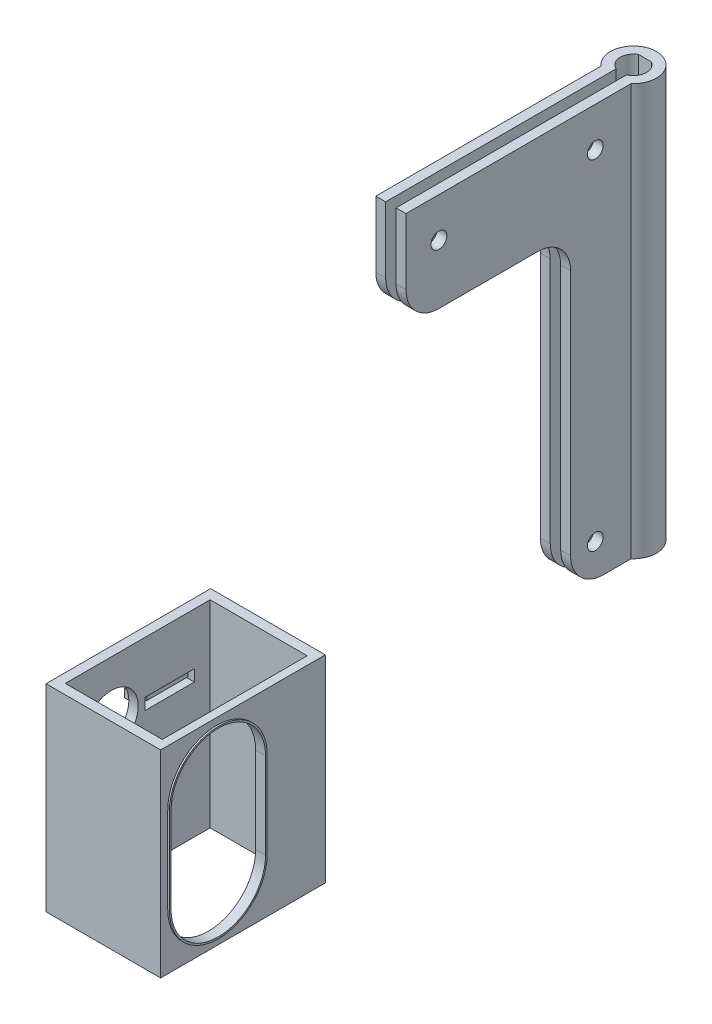
SolidWorks part; units mm, degrees
ref_plane "Front Plane" through (0, 0, 0) normal (0, 0, 1) x (1, 0, 0)
ref_plane "Top Plane" through (0, 0, 0) normal (0, 1, 0) x (1, 0, 0)
ref_plane "Right Plane" through (0, 0, 0) normal (1, 0, 0) x (0, 0, -1)
ref_plane "ULTRASONIC CENTER" through (0, 0, 125) normal (0, 0, 1) x (1, 0, 0)
sketch "Sketch1" plane through (0, 0, 0) normal (0, 1, 0) x (1, 0, 0)
  line L0 (-1.5875, -3.6715) -> (-1.5875, -23.6715)
  line L1 (1.5875, -3.6715) -> (1.5875, -23.6715)
  line L2 (1.9365, 3.5) -> (-1.9365, 3.5)
  line L3 (4.5875, -5.2872) -> (4.5875, -23.6715)
  line L4 (-4.5875, -5.2872) -> (-4.5875, -23.6715)
  line L5 (-4.5875, -23.6715) -> (-1.5875, -23.6715)
  line L6 (1.5875, -23.6715) -> (4.5875, -23.6715)
  arc A0 (1.5875, -3.6715) -> (1.9365, 3.5) centre (0, 0) ccw
  arc A1 (4.5875, -5.2872) -> (-4.5875, -5.2872) centre (0, 0) ccw
  arc A2 (-1.9365, 3.5) -> (-1.5875, -3.6715) centre (0, 0) ccw
  arc A4 (1.5875, -3.6715) -> (-1.5875, -3.6715) centre (0, 0) ccw construction
  dimension "D1" = 4
  dimension "D2" = 20
  dimension "D3" = 3.5
  dimension "D5" = 3.175
  dimension "D4" = 3
extrude "Boss-Extrude1" add sketch "Sketch1" along normal blind 125
ref_plane "PADDLE CENTER" through (0, 0, 0) normal (-1, 0, 0) x (0, 0, 1)
ref_plane "DISC CENTER" through (0, -15, 0) normal (0, 1, 0) x (1, 0, 0)
ref_axis "Axis1" through (0, -15, 24.6715) along (0, 0, -1)
ref_plane "OFFSET" through (-36.4125, 0, 0) normal (-1, 0, 0) x (0, 0, 1)
ref_plane "PADDLE SURFACE" through (-1.5875, 0, 0) normal (1, 0, 0) x (0, 0, -1)
ref_axis "Axis2" through (-36.4125, -15, -8.5336) along (0, 0, 1)
ref_point "ULTRASONIC"
sketch "Sketch5" plane through (0, 125, 0) normal (0, 1, 0) x (1, 0, 0)
  line L1 (-1.5875, -111.5) -> (-1.5875, -106.5)
  line L2 (-47.5875, -106.5) -> (-47.5875, -141.5)
  line L3 (-47.5875, -141.5) -> (-1.5875, -141.5)
  line L4 (-1.5875, -141.5) -> (-1.5875, -136.5)
  line L5 (-1.5875, -136.5) -> (-42.5875, -136.5)
  line L9 (-1.5875, -23.6715) -> (-1.5875, -3.6715) construction
  line L10 (-42.5875, -111.5) -> (-1.5875, -111.5)
  line L12 (-42.5875, -136.5) -> (-42.5875, -111.5)
  line L13 (-47.5875, -106.5) -> (-1.5875, -106.5)
  line L18 (-18.6703, -4) -> (17.7565, -4) construction
  circle A0 centre (0, 0) radius 4 construction
  arc A1 (-1.9365, 3.5) -> (-1.5875, -3.6715) centre (0, 0) ccw construction
  point P2 (-42.5875, -124)
  dimension "D2" = 120
  dimension "D1" = 41
  dimension "D3" = 25
  dimension "D4" = 5
  dimension "D5" = 5
  dimension "D7" = 5
extrude "Boss-Extrude2" [suppressed] add sketch "Sketch5" against normal mid plane 30 from offset 137.5 offset against normal yes
sketch "Sketch6" plane through (0, 125, 0) normal (0, 1, 0) x (1, 0, 0)
  line L0 (4.5875, -23.6715) -> (4.5875, -5.2872) construction
  line L1 (1.5875, -23.6715) -> (4.5875, -23.6715)
  line L2 (1.5875, -23.6715) -> (1.5875, -73.6715)
  line L3 (1.5875, -73.6715) -> (4.5875, -73.6715)
  line L4 (4.5875, -23.6715) -> (4.5875, -73.6715)
  line L6 (-1.5875, -23.6715) -> (-1.5875, -3.6715) construction
  line L7 (-4.5875, -23.6715) -> (-1.5875, -23.6715)
  line L8 (-4.5875, -23.6715) -> (-4.5875, -73.6715)
  line L9 (-4.5875, -73.6715) -> (-1.5875, -73.6715)
  line L10 (-1.5875, -23.6715) -> (-1.5875, -73.6715)
  dimension "D1" = 50
extrude "Boss-Extrude3" add sketch "Sketch6" against normal blind 30
fillet "Fillet6" radius 10 6 edges at (3.0875, 0, 23.6715) (-3.0875, 0, 23.6715) (3.0875, 95, 73.6715) (-3.0875, 95, 73.6715) (3.0875, 95, 23.6715) (-3.0875, 95, 23.6715)
hole_wizard "M4 Clearance Hole1" positions "Sketch2" profile "Sketch3" hole size "M4" standard "ANSI Metric" end condition through all
sketch "Sketch2" plane through (4.5875, 0, 0) normal (1, 0, 0) x (0, 0, -1)
  line L4 (-73.6715, 125) -> (-5.2872, 125) construction
  line L6 (-73.6715, 105) -> (-73.6715, 125) construction
  point P0 (-16.1715, 113)
  point P4 (-16.1715, 10)
  point P19 (-63.6715, 113)
  dimension "D1" = 103
  dimension "D2" = 12
  dimension "D3" = 47.5
  dimension "D4" = 10
sketch "Sketch3" plane through (4.5875, 113, 16.1715) normal (0, 1, 0) x (0, 0, -1)
  line L0 (0, 0) -> (0, 11.5875)
  line L1 (0, 11.5875) -> (2.4, 11.5875)
  line L2 (2.4, 11.5875) -> (2.4, 0)
  line L5 (2.4, 0) -> (0, 0)
  line L11 (0, -6.35) -> (0, 107.95) construction
  dimension "Thru Hole Dia." = 4.8
  dimension "Thru Hole Depth" = 11.5875
sketch "Sketch9" [suppressed] plane through (-1.5875, 0, 0) normal (1, 0, 0) x (0, 0, -1)
  line L0 (-105.675, 2.5) -> (-22.7496, 2.5)
  line L1 (-105.675, 2.5) -> (-105.675, -27.5)
  line L2 (-105.675, -27.5) -> (-22.7496, -27.5)
  line L3 (-22.7496, 95) -> (-22.7496, 0) construction
  line L5 (-4.1335, 0) -> (-4.1335, -27.5)
  line L6 (-4.1335, -27.5) -> (-22.7496, -27.5)
  line L7 (-22.7496, 2.5) -> (-22.7496, 0)
  line L8 (-22.7496, 95) -> (-22.7496, 0) construction
  line L9 (-22.7496, 0) -> (-4.1335, 0) construction
  line L10 (-22.7496, 0) -> (-4.1335, 0)
extrude "Boss-Extrude5" [suppressed] add sketch "Sketch9" against normal up to surface (3 mm away) up to face at (-4.5875, 113, 13.7715)
chamfer "Chamfer2" [suppressed] distance 42 distance2 35
fillet "Fillet1" [suppressed] radius 40
fillet "Fillet2" [suppressed] radius 10
sketch "Sketch11" plane through (0, 125, 0) normal (0, 1, 0) x (1, 0, 0)
  line L0 (-21.2191, -4) -> (29.064, -4) construction
  line L1 (4.5875, -66.5) -> (47.5875, -66.5)
  line L2 (4.5875, -73.6715) -> (4.5875, -5.2872) construction
  line L3 (47.5875, -66.5) -> (47.5875, -101.5)
  line L4 (47.5875, -101.5) -> (4.5875, -101.5)
  line L5 (4.5875, -101.5) -> (4.5875, -96.5)
  line L6 (4.5875, -96.5) -> (42.5875, -96.5)
  line L7 (42.5875, -96.5) -> (42.5875, -71.5)
  line L8 (42.5875, -71.5) -> (4.5875, -71.5)
  line L9 (4.5875, -71.5) -> (4.5875, -66.5)
  line L10 (1.5875, -3.6715) -> (1.5875, -73.6715) construction
  circle A0 centre (0, 0) radius 4 construction
  arc A1 (-1.9365, 3.5) -> (-1.5875, -3.6715) centre (0, 0) ccw construction
  point P17 (42.5875, -84)
  dimension "D1" = 5
  dimension "D2" = 5
  dimension "D3" = 5
  dimension "D4" = 41
  dimension "D5" = 80
  dimension "D6" = 25
extrude "Boss-Extrude6" [suppressed] add sketch "Sketch11" along normal mid plane 30 from offset 137.5 offset against normal yes
sketch "Sketch13" [suppressed] plane through (4.5875, 0, 0) normal (-1, 0, 0) x (0, 0, 1)
  line L0 (70.675, 2.5) -> (22.7496, 2.5)
  line L1 (22.7496, 55) -> (22.7496, 42.5) construction
  line L2 (22.7496, 2.5) -> (22.7496, 0)
  line L3 (22.7496, 0) -> (4.1335, 0)
  line L4 (70.675, 2.5) -> (70.675, -27.5)
  line L5 (70.675, -27.5) -> (4.1335, -27.5)
  line L6 (4.1335, -27.5) -> (4.1335, 0)
extrude "Boss-Extrude8" [suppressed] add sketch "Sketch13" along normal up to surface (3 mm away) up to face at (1.5875, 113, 13.7715)
chamfer "Chamfer3" [suppressed] distance 42 distance2 35
fillet "Fillet5" [suppressed] radius 40
fillet "Fillet4" [suppressed] radius 10
sketch "Sketch14" [suppressed] plane through (0, 0, 110.675) normal (0, 0, 1) x (1, 0, 0)
  line L5 (-47.5875, -27.5) -> (-47.5875, 2.5) construction
  line L6 (-40.0875, -7.5) -> (-40.0875, -17.5) construction
  line L7 (-37.5875, -7.5) -> (-37.5875, -17.5)
  line L8 (-42.5875, -7.5) -> (-42.5875, -17.5)
  line L9 (-42.5875, -27.5) -> (-42.5875, 2.5) construction
  arc A0 (-37.5875, -7.5) -> (-42.5875, -7.5) centre (-40.0875, -7.5) ccw
  arc A1 (-42.5875, -17.5) -> (-37.5875, -17.5) centre (-40.0875, -17.5) ccw
  point P2 (-40.0875, -12.5)
  point P9 (-47.5875, -12.5)
  dimension "D1" = 5
  dimension "D2" = 10
extrude "Cut-Extrude1" [suppressed] cut sketch "Sketch14" against normal up to next
sketch "Sketch15" [suppressed] plane through (0, 0, 70.675) normal (0, 0, 1) x (1, 0, 0)
  line L0 (40.0875, -7.5) -> (40.0875, -17.5) construction
  line L1 (42.5875, -7.5) -> (42.5875, -17.5)
  line L2 (37.5875, -7.5) -> (37.5875, -17.5)
  line L3 (42.5875, 2.5) -> (42.5875, -27.5) construction
  arc A0 (42.5875, -7.5) -> (37.5875, -7.5) centre (40.0875, -7.5) ccw
  arc A1 (37.5875, -17.5) -> (42.5875, -17.5) centre (40.0875, -17.5) ccw
  point P2 (40.0875, -12.5)
  point P9 (42.5875, -12.5)
  dimension "D1" = 5
  dimension "D2" = 10
extrude "Cut-Extrude2" [suppressed] cut sketch "Sketch15" against normal up to next
sketch "Sketch16" plane through (-36.4125, 0, 0) normal (-1, 0, 0) x (0, 0, 1)
  line L0 (125, 15) -> (125, -45) construction
  line L1 (92, 15) -> (142, 15)
  line L3 (92, -45) -> (142, -45)
  line L4 (142, 15) -> (142, -45)
  line L5 (92, 15) -> (142, -45) construction
  line L6 (92, -45) -> (142, 15) construction
  line L7 (132.5, -11) -> (132.5, -19) construction
  line L12 (92, 15) -> (92, -45)
  line L13 (134.75, -11) -> (134.75, -19)
  line L14 (130.25, -11) -> (130.25, -19)
  line L15 (116.35, -10) -> (116.35, -20) construction
  line L16 (117.35, -10) -> (117.35, -20)
  line L17 (115.35, -10) -> (115.35, -20)
  circle A0 centre (125, -2) radius 8.15
  circle A1 centre (125, -28) radius 8.15
  arc A4 (134.75, -11) -> (130.25, -11) centre (132.5, -11) ccw
  arc A5 (130.25, -19) -> (134.75, -19) centre (132.5, -19) ccw
  arc A6 (117.35, -10) -> (115.35, -10) centre (116.35, -10) ccw
  arc A7 (115.35, -20) -> (117.35, -20) centre (116.35, -20) ccw
  point P1 (117, -15)
  point P14 (125, -15)
  point P15 (132.5, -15)
  point P26 (116.35, -15)
  dimension "D4" = 16.3
  dimension "D5" = 16.3
  dimension "D1" = 60
  dimension "D3" = 50
  dimension "D6" = 26
  dimension "D7" = 13
  dimension "D2" = 17
  dimension "D8" = 7.5
  dimension "D10" = 4.5
  dimension "D11" = 8
  dimension "D12" = 8.65
  dimension "D13" = 2
  dimension "D14" = 10
extrude "Boss-Extrude9" add sketch "Sketch16" against normal blind 2.85 separate body contours L3 L4 L1 L12 A1 A0 region at (-36.4125, 14.219, 117)
sketch "Sketch19" plane through (-33.5625, 0, 0) normal (1, 0, 0) x (0, 0, -1)
  line L0 (-92, -45) -> (-142, -45) construction
  line L9 (-142, 15) -> (-139.5, 15)
  line L10 (-142, 15) -> (-142, -45)
  line L11 (-142, -45) -> (-139.5, -45)
  line L12 (-139.5, 15) -> (-139.5, -45)
  line L13 (-92, 15) -> (-142, 15) construction
  line L14 (-92, -45) -> (-94.5, -45)
  line L15 (-92, -45) -> (-92, 15)
  line L16 (-92, 15) -> (-94.5, 15)
  line L17 (-94.5, -45) -> (-94.5, 15)
  dimension "D1" = 2.5
  dimension "D2" = 2.5
extrude "Boss-Extrude11" add sketch "Sketch19" along normal up to surface (31.975 mm away) up to plane "PADDLE SURFACE"
sketch "Sketch20" plane through (0, -45, 0) normal (0, -1, 0) x (1, 0, 0)
  line L0 (-1.5875, 92) -> (-36.4125, 92) construction
  line L1 (-1.5875, 142) -> (-4.0875, 142)
  line L2 (-1.5875, 142) -> (-1.5875, 92)
  line L3 (-1.5875, 92) -> (-4.0875, 92)
  line L4 (-4.0875, 142) -> (-4.0875, 92)
  dimension "D1" = 2.5
extrude "Boss-Extrude12" add sketch "Sketch20" against normal up to surface (60 mm away) up to face at (-18.2875, 15, 117)
sketch "Sketch21" plane through (-1.5875, 0, 0) normal (1, 0, 0) x (0, 0, -1)
  line L0 (-125, -1.9) -> (-125, -28.1) construction
  line L1 (-125, 55) -> (-125, -55) construction
  line L2 (-110, -1.9) -> (-110, -28.1) construction
  line L3 (-140, -1.9) -> (-140, -28.1) construction
  line L4 (-110.15, -1.9) -> (-110.15, -28.1)
  line L5 (-139.85, -1.9) -> (-139.85, -28.1)
  line L6 (-110.65, -1.9) -> (-110.65, -28.1)
  line L7 (-139.35, -1.9) -> (-139.35, -28.1)
  arc A0 (-110, -1.9) -> (-140, -1.9) centre (-125, -1.9) ccw construction
  arc A1 (-140, -28.1) -> (-110, -28.1) centre (-125, -28.1) ccw construction
  arc A2 (-139.85, -28.1) -> (-110.15, -28.1) centre (-125, -28.1) ccw
  arc A3 (-110.15, -1.9) -> (-139.85, -1.9) centre (-125, -1.9) ccw
  arc A4 (-139.35, -28.1) -> (-110.65, -28.1) centre (-125, -28.1) ccw
  arc A5 (-110.65, -1.9) -> (-139.35, -1.9) centre (-125, -1.9) ccw
  point P5 (-125, -15)
  dimension "D1" = 26.2
  dimension "D2" = 30
  dimension "D3" = 0.15
  dimension "D4" = 0.5
extrude "Cut-Extrude3" cut sketch "Sketch21<2>" against normal up to next (2.5 mm away) contours L6 A5 L7 A4 region at (-1.5875, -15, 125)
sketch "Sketch21<2>" plane through (-1.5875, 0, 0) normal (1, 0, 0) x (0, 0, -1) same geometry as "Sketch21"
extrude "Boss-Extrude13" add sketch "Sketch21" along normal blind 0.5
sketch "Sketch18" plane through (0, -45, 0) normal (0, -1, 0) x (1, 0, 0)
  line L0 (-1.5875, -68.75) -> (-1.5875, 68.75) construction
  line L1 (-36.4125, 142) -> (-1.5875, 142)
  line L2 (-36.4125, 142) -> (-36.4125, 139)
  line L3 (-36.4125, 139) -> (-1.5875, 139)
  line L4 (-1.5875, 142) -> (-1.5875, 139)
  line L6 (-36.4125, 92) -> (-1.5875, 92)
  line L7 (-36.4125, 92) -> (-36.4125, 95)
  line L8 (-36.4125, 95) -> (-1.5875, 95)
  line L9 (-1.5875, 92) -> (-1.5875, 95)
  dimension "D1" = 3
  dimension "D2" = 3
extrude "Boss-Extrude10" add sketch "Sketch18" against normal up to surface (60 mm away) up to face at (-18.825, 15, 117)
sketch "Sketch22" plane through (-36.4125, 0, 0) normal (-1, 0, 0) x (0, 0, 1)
  line L0 (99.8, -1.25) -> (99.8, -0.75)
  line L1 (99.8, -0.75) -> (114.8, -0.75)
  line L2 (114.8, -0.75) -> (114.8, -4.25)
  line L3 (114.8, -4.25) -> (99.8, -4.25)
  line L4 (99.8, -4.25) -> (99.8, -3.75)
  line L5 (99.8, -3.75) -> (114.3, -3.75)
  line L6 (114.3, -3.75) -> (114.3, -1.25)
  line L7 (114.3, -1.25) -> (99.8, -1.25)
  line L8 (125, -23.8769) -> (125, 23.8769) construction
  line L10 (117.35, -10) -> (117.35, -20) construction
  point P8 (114.8, -2.5)
  point P15 (117.35, -15)
  dimension "D1" = 2.5
  dimension "D2" = 0.5
  dimension "D3" = 0.5
  dimension "D4" = 15
  dimension "D5" = 10.7
  dimension "D6" = 12.5
extrude "Cut-Extrude4" cut sketch "Sketch22" against normal up to surface (2.85 mm away) up to face at (-33.5625, -15, 116.35)
sketch "Sketch25" plane through (0, -3.75, 0) normal (0, -1, 0) x (1, 0, 0)
  line L0 (-36.4125, 114.3) -> (-38.0125, 114.3)
  line L1 (-38.0125, 114.3) -> (-38.0125, 115.05)
  line L2 (-38.0125, 115.05) -> (-39.5125, 115.05)
  line L3 (-39.5125, 115.05) -> (-39.5125, 113.3)
  line L4 (-39.5125, 113.3) -> (-36.4125, 110.2)
  line L5 (-36.4125, 114.3) -> (-36.4125, 99.8) construction
  line L6 (-36.4125, 110.2) -> (-36.4125, 114.3)
  point P1 (-37.6975, 114.3)
  point P10 (-39.0125, 113.7084)
  point P11 (-38.0125, 114.3)
  point P12 (-38.0125, 114.3386)
  point P13 (-39.0125, 113.3)
  point P14 (-39.0125, 115.1671)
  dimension "D1" = 1
  dimension "D2" = 1.5
  dimension "D3" = 1.6
  dimension "D4" = 45
  dimension "D5" = 0.75
extrude "Boss-Extrude16" add sketch "Sketch25" against normal up to surface (2.5 mm away) up to face at (-34.9875, -1.25, 107.05)
sketch "Sketch26" plane through (-33.5625, 0, 0) normal (1, 0, 0) x (0, 0, -1)
  line L1 (-114.8, -0.75) -> (-99.8, -0.75)
  line L2 (-114.8, -0.75) -> (-114.8, -4.25)
  line L3 (-114.8, -4.25) -> (-99.8, -4.25)
  line L4 (-99.8, -0.75) -> (-99.8, -4.25)
extrude "Cut-Extrude5" cut sketch "Sketch26" against normal offset from surface (1.85 mm away) 1 up to face at (-36.4125, -2.5, 106.15)
chamfer "Chamfer4" distance 2 angle 45 1 edges at (-35.4125, -2.5, 114.3)
equation "\"D7@Sketch16\"=\"D6@Sketch16\"/2"
